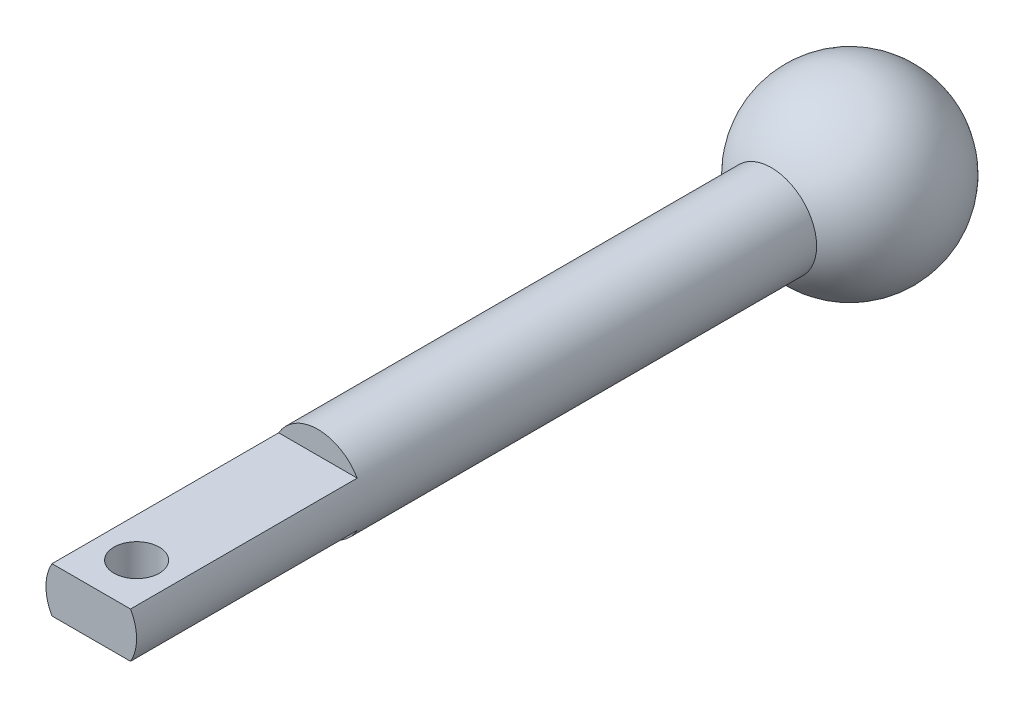
SolidWorks part; units mm, degrees
ref_plane "Front Plane" through (0, 0, 0) normal (0, 0, 1) x (1, 0, 0)
ref_plane "Top Plane" through (0, 0, 0) normal (0, 1, 0) x (1, 0, 0)
ref_plane "Right Plane" through (0, 0, 0) normal (1, 0, 0) x (0, 0, -1)
sketch "Sketch1" plane through (0, 0, 0) normal (0, 1, 0) x (1, 0, 0)
  line L0 (0, 9.5) -> (0, 33.4641) construction
  line L3 (0, 0) -> (2, 0)
  line L4 (2, 30) -> (2, 0)
  line L5 (0, 37.4641) -> (0, 9.5)
  line L6 (0, 9.5) -> (0, 0)
  arc A0 (2, 30) -> (0, 37.4641) centre (0, 33.4641) ccw
  dimension "D1" = 4
  dimension "D4" = 30
  dimension "D2" = 2
revolve "Revolve1" add sketch "Sketch1" angle 360 about L0
ref_plane "Plane1" through (0, 2, 0) normal (0, 1, 0) x (1, 0, 0)
sketch "Sketch2" plane through (0, 2, 0) normal (0, 1, 0) x (1, 0, 0)
  line L0 (-2, 0) -> (2, 0) construction
  line L1 (5, 10) -> (-5, 10)
  line L2 (5, 10) -> (5, 0)
  line L3 (5, 0) -> (-5, 0)
  line L4 (-5, 10) -> (-5, 0)
  line L5 (5, 10) -> (-5, 0) construction
  line L6 (5, 0) -> (-5, 10) construction
  line L7 (0, 7.25) -> (0, -0.8477) construction
  point P8 (0, 5)
  dimension "D1" = 10
  dimension "D2" = 10
extrude "Cut-Extrude1" cut sketch "Sketch2" against normal blind 1
sketch "Sketch3" plane through (0, 0, 0) normal (0, 1, 0) x (1, 0, 0)
  line L3 (5, 0) -> (-5, 0) construction
  circle A0 centre (0, 2) radius 1
  point P2 (0, 0)
  dimension "D1" = 2
  dimension "D2" = 2
extrude "Cut-Extrude2" cut sketch "Sketch3" against normal through all both and the other way through all
mirror "Mirror1" about plane through (0, 0, 0) normal (0, 1, 0) of "Cut-Extrude1"
